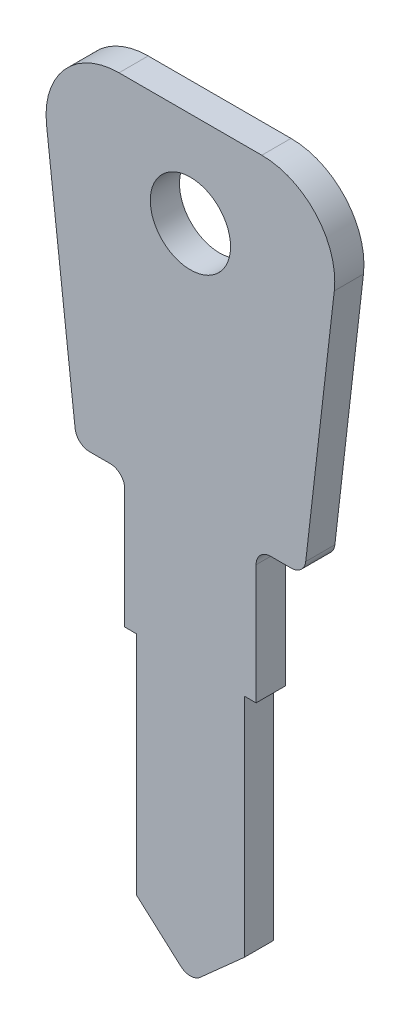
SolidWorks part; units mm, degrees
ref_plane "前视基准面" through (0, 0, 0) normal (0, 0, 1) x (1, 0, 0)
ref_plane "上视基准面" through (0, 0, 0) normal (0, 1, 0) x (1, 0, 0)
ref_plane "右视基准面" through (0, 0, 0) normal (1, 0, 0) x (0, 0, -1)
sketch "草图1" plane through (0, 0, 0) normal (0, 0, 1) x (1, 0, 0)
  line L0 (0, 68.987) -> (0, -54.2213) construction
  line L1 (-56.6306, 0) -> (42.6142, 0) construction
  line L2 (-7.9018, 0.8859) -> (-9.86, 17.9293)
  line L3 (-4.8926, 23.5) -> (4.8926, 23.5)
  line L4 (-6.9083, 0) -> (-5.5, 0)
  line L5 (-4.5, -1) -> (-4.5, -9.2)
  line L6 (-4.5, -9.2) -> (-3.7, -9.2)
  line L7 (-3.7, -9.2) -> (-3.7, -24.7)
  line L8 (-3.7, -24.7) -> (0, -28)
  line L9 (3.7, -24.7) -> (0, -28)
  line L10 (3.7, -9.2) -> (3.7, -24.7)
  line L11 (4.5, -9.2) -> (3.7, -9.2)
  line L12 (4.5, -1) -> (4.5, -9.2)
  line L13 (6.9083, 0) -> (5.5, 0)
  line L14 (7.9018, 0.8859) -> (9.86, 17.9293)
  arc A0 (-9.86, 17.9293) -> (-4.8926, 23.5) centre (-4.8926, 18.5) cw
  arc A1 (-7.9018, 0.8859) -> (-6.9083, 0) centre (-6.9083, 1) ccw
  arc A2 (-5.5, 0) -> (-4.5, -1) centre (-5.5, -1) cw
  arc A3 (5.5, 0) -> (4.5, -1) centre (5.5, -1) ccw
  arc A4 (7.9018, 0.8859) -> (6.9083, 0) centre (6.9083, 1) cw
  arc A5 (9.86, 17.9293) -> (4.8926, 23.5) centre (4.8926, 18.5) ccw
  point P15 (-10.5, 23.5)
  point P18 (-7.8, 0)
  point P21 (-4.5, 0)
  point P34 (0, 23.5)
  dimension "D9" = 5
  dimension "D10" = 1
  dimension "D11" = 1
  dimension "D1" = 23.5
  dimension "D2" = 10.5
  dimension "D3" = 51.5
  dimension "D4" = 4.5
  dimension "D5" = 9.2
  dimension "D6" = 7.8
  dimension "D7" = 15.5
  dimension "D8" = 3.7
extrude "凸台-拉伸1" add sketch "草图1" along normal blind 1 and the other way blind 1
fillet "圆角1" radius 1 1 edges at (0, -28, 0)
sketch "草图2" plane through (0, 0, 1) normal (0, 0, 1) x (1, 0, 0)
  line L0 (0, 29.7423) -> (0, -37.4968) construction
  line L1 (4.8926, 23.5) -> (-4.8926, 23.5) construction
  circle A0 centre (0, 17) radius 2.75
  dimension "D1" = 5.5
  dimension "D2" = 6.5
extrude "切除-拉伸1" cut sketch "草图2" against normal blind 2
